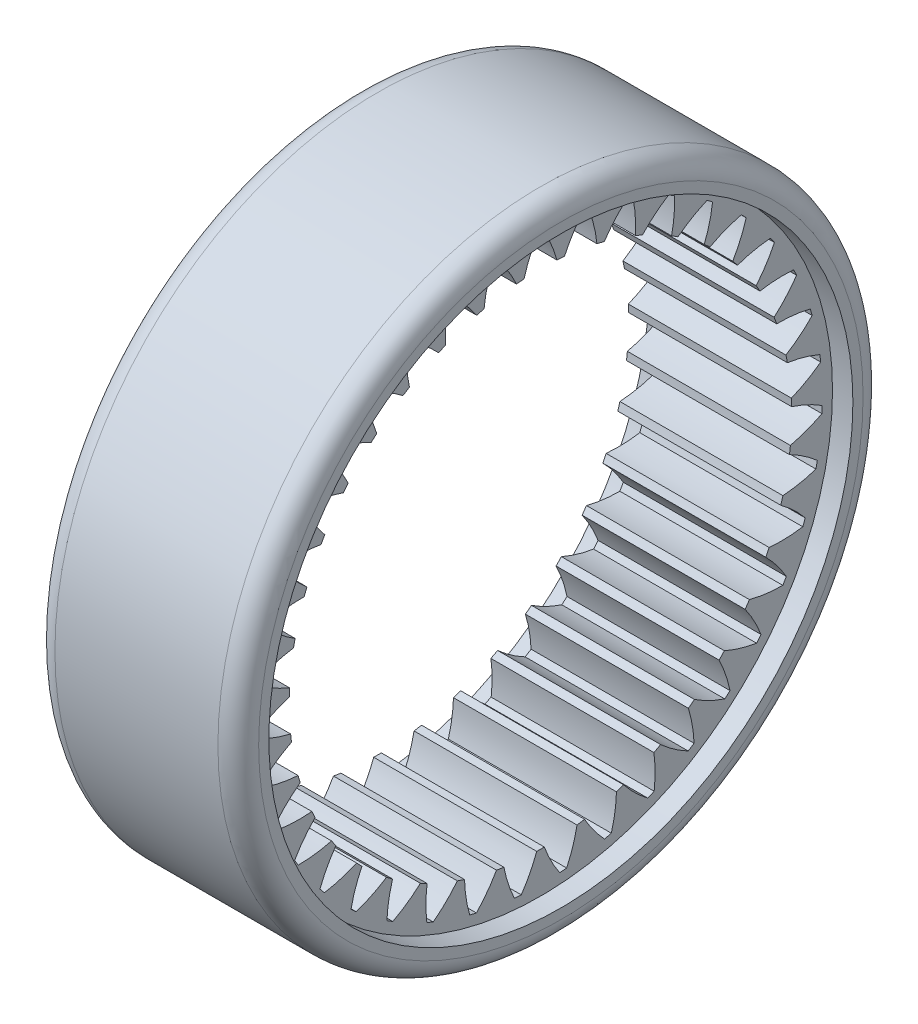
SolidWorks part; units mm, degrees
ref_plane "Plane1" through (0, 0, 0) normal (0, 0, 1) x (1, 0, 0)
ref_plane "Plane2" through (0, 0, 0) normal (0, 1, 0) x (1, 0, 0)
ref_plane "Plane3" through (0, 0, 0) normal (1, 0, 0) x (0, 0, -1)
other "Configuration Table"
sketch "HoldingSke" plane through (0, 0, 0) normal (0, 1, 0) x (1, 0, 0)
  line L0 (0, 0) -> (0.3886, -0.3147)
  line L1 (-15, 0) -> (100, 0) construction
  line L2 (0, 0) -> (-2.1039, 2.3779)
  line L3 (0, 0) -> (-11.863, 4.5341)
  line L4 (0, 0) -> (6.7114, 5.4348)
  line L5 (0, 0) -> (-23.7986, -8.8762)
  line L6 (0, 0) -> (-10.5278, -7.1032)
  line L7 (-2.1039, 2.3779) -> (3.3635, 27.1825)
  line L8 (-76.2, 4.3779) -> (-54.61, 4.3779)
  line L9 (-71.009, 38.7566) -> (-53.1078, 45.2721)
  line L10 (-76.2, 71.12) -> (104.1128, 71.12)
  line L11 (0, 0) -> (-30, 0)
  line L12 (-76.2, 101.6) -> (-76.133, 101.6)
  line L13 (24.9733, 27.94) -> (52.9518, 28.4284)
  line L14 (24.9733, 27.94) -> (24.9743, 27.94)
  line L15 (24.9733, 27.94) -> (100.4006, 29.5858)
  circle A0 centre (0, 0) radius 47.5
  circle A1 centre (0, 0) radius 12.7
  circle A2 centre (0, 0) radius 12.7
  dimension "Num_teeth" = 39
  dimension "Pitch_radius" = 180.3128
  dimension "Width" = 30
  dimension "Diameter" = 95
sketch "BasProSke" plane through (0, 0, 0) normal (0, 1, 0) x (1, 0, 0)
  line L0 (-10, 0) -> (60, 0) construction
  line L1 (0, 37) -> (0, 47.5)
  line L2 (0, 37) -> (30, 37)
  line L3 (30, 37) -> (30, 47.5)
  line L4 (30, 47.5) -> (0, 47.5)
  dimension "Thickness" = 30
  dimension "Diameter" = 95
revolve "Base-Revolve" add sketch "BasProSke" angle 360 about L0
sketch "TooCutSke" plane through (0, 0, 0) normal (1, 0, 0) x (0, 0, -1)
  line L3 (1.7379, 38.9613) -> (1.7379, 53.6633) construction
  line L4 (0, 0) -> (0, 59.563) construction
  line L5 (0, 0) -> (-5.4981, 68.1059) construction
  line L6 (-16.3867, 31.7676) -> (35.066, 35.9213) construction
  circle A0 centre (0, 0) radius 39 construction
  circle A1 centre (0, 0) radius 41.501 construction
  circle A2 centre (0, 0) radius 32.9832 construction
  circle A3 centre (0, 0) radius 36.9746 construction
  arc A4 (2.4271, 36.8949) -> (0.5122, 41.4978) centre (-16.3867, 31.7676) ccw
  arc A5 (2.4271, 36.8949) -> (-2.4271, 36.8949) centre (0, 0) ccw
  arc A6 (0.5122, 41.4978) -> (-0.5122, 41.4978) centre (0, 0) ccw
  arc A7 (-0.5122, 41.4978) -> (-2.4271, 36.8949) centre (16.3867, 31.7676) ccw
extrude "ToothCut" cut sketch "TooCutSke" along normal through all
fillet "Breaks" [suppressed] radius 0.2
fillet "RootFillets" [suppressed] radius 0.501
pattern_circular "TeethCuts" count 39 every 9.231 about axis through (-10, 0, 0) along (1, 0, 0) of "RootFillets", "Breaks", "ToothCut"
sketch "Sketch1" plane through (30, 0, 0) normal (1, 0, 0) x (0, 0, -1)
  circle A0 centre (0, 0) radius 43
  dimension "D1" = 86
extrude "Cut-Extrude1" cut sketch "Sketch1" against normal blind 3
sketch "Sketch2" plane through (0, 0, 0) normal (-1, 0, 0) x (0, 0, 1)
  circle A0 centre (0, 0) radius 43
  dimension "D1" = 86
extrude "Cut-Extrude2" cut sketch "Sketch2" against normal blind 3
fillet "Fillet1" radius 3 2 edges at (0, 0, 47.5) (30, 0, 47.5)
equation "' \"Module@HoldingSke\" = 6.35"
equation "' \"Num_teeth@HoldingSke\" = 24"
equation "' \"Ap@HoldingSke\" =  14.5"
equation "' \"Ap@HoldingSke\" = 14.5"
equation "' \"Width@HoldingSke\" = 12"
equation "' \"Diameter@HoldingSke\" = 8 * 25.4"
equation "' \"Show_teeth@HoldingSke\" = 100"
equation "' \"Backlash@HoldingSke\" = 0.009 * 25.4"
equation "' \"Addendum_fac@HoldingSke\" = 1.0"
equation "' \"Dedendum_fac@HoldingSke\" = 1.25"
equation "' \"Dedendum_add@HoldingSke\" = 0.00005 * 25.4"
equation "' \"Clearance_fac@HoldingSke\" = 0.25"
equation "\"Pitch@HoldingSke\" = 1 / \"Module@HoldingSke\" "
equation "\"Overcut_dia@TooCutSke\" = (\"Num_teeth@HoldingSke\" - 2 * \"Addendum_fac@HoldingSke\") / \"Pitch@HoldingSke\" - 0.002 * 25.4"
equation "\"Pitch_dia@TooCutSke\" = \"Num_teeth@HoldingSke\" / \"Pitch@HoldingSke\""
equation "\"Base_dia@TooCutSke\" = \"Num_teeth@HoldingSke\" / \"Pitch@HoldingSke\" * cos((\"Ap@HoldingSke\"  * 3.14159265 / 180)) * 0.90"
equation "\"Root_dia@TooCutSke\" = \"Num_teeth@HoldingSke\"  / \"Pitch@HoldingSke\" + 2 *  \"Dedendum_fac@HoldingSke\"/ \"Pitch@HoldingSke\" + \"Dedendum_add@HoldingSke\" * 2"
equation "\"Half_ang@TooCutSke\" = 180 / \"Num_teeth@HoldingSke\""
equation "\"Half_CT@TooCutSke\" = \"Num_teeth@HoldingSke\" / \"Pitch@HoldingSke\" * sin((3.14159265 / 2 / \"Num_teeth@HoldingSke\")) / 2 + 10 * \"Backlash@HoldingSke\" / 4"
equation "\"Flank_rad@TooCutSke\" = \"Num_teeth@HoldingSke\" / \"Pitch@HoldingSke\" / 4"
equation "\"Radius@RootFillets\"= \"Clearance_fac@HoldingSke\" / \"Pitch@HoldingSke\" + \"Dedendum_add@HoldingSke\""
equation "\"Break_rad@Breaks\" = 0.02 / \"Pitch@HoldingSke\" * 5"
equation "\"Num_teeth@TeethCuts\" = int( \"Show_teeth@HoldingSke\" ) + 1"
equation "\"Num_teeth@TeethCuts\" = ((sgn( \"Num_teeth@TeethCuts\" - \"Num_teeth@HoldingSke\" )-1)*( \"Num_teeth@TeethCuts\" - \"Num_teeth@HoldingSke\" ))/-2+ \"Num_teeth@HoldingSke\""
equation "\"Num_teeth@TeethCuts\" = ((sgn( \"Num_teeth@TeethCuts\" - 2.0)+1)*( \"Num_teeth@TeethCuts\" - 2.0))/2 +2.0"
equation "\"Angle@TeethCuts\" = 360.0 / \"Num_teeth@HoldingSke\""
equation "\"Diameter@BasProSke\" = \"Num_teeth@HoldingSke\"  / \"Pitch@HoldingSke\" + 2 *  \"Dedendum_fac@HoldingSke\"/ \"Pitch@HoldingSke\" + \"Dedendum_add@HoldingSke\" * 2 + 0.002 * 25.4"
equation "\"Diameter@BasProSke\" = ((sgn( \"Diameter@BasProSke\"  - \"Diameter@HoldingSke\" )+1)*( \"Diameter@BasProSke\"  - \"Diameter@HoldingSke\" ))/2 + \"Diameter@HoldingSke\""
equation "\"Inside_diameter@BasProSke\" =  (\"Num_teeth@HoldingSke\" - 2 * \"Addendum_fac@HoldingSke\") / \"Pitch@HoldingSke\" "
equation "\"Thickness@BasProSke\"  = \"Width@HoldingSke\""
